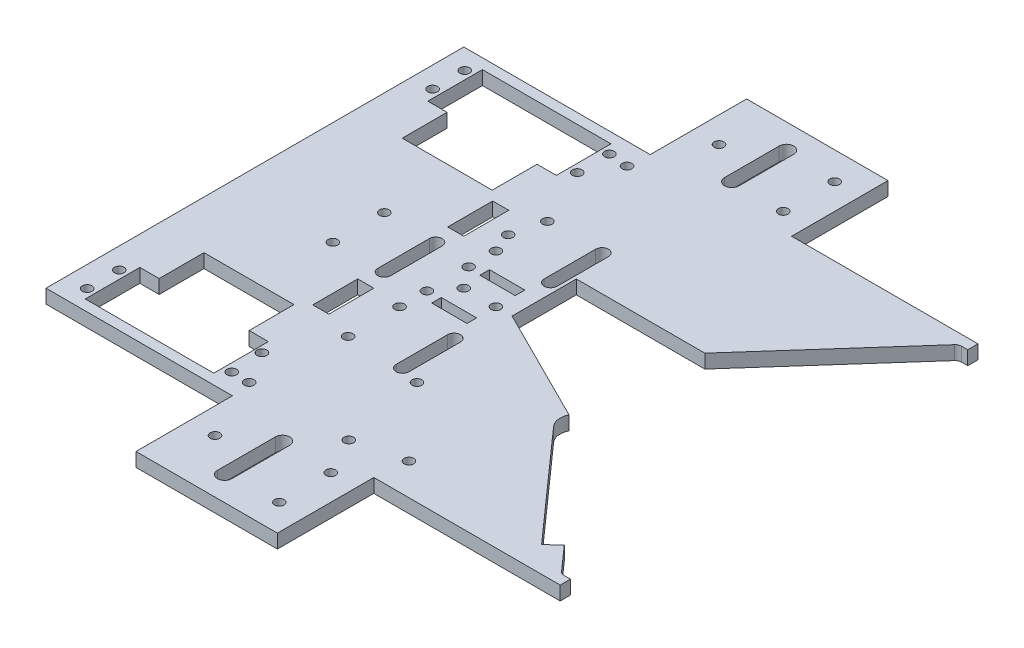
SolidWorks part; units mm, degrees
material "Acrylic (Medium-high impact)"
ref_plane "Front Plane" through (0, 0, 0) normal (0, 0, 1) x (1, 0, 0)
ref_plane "Top Plane" through (0, 0, 0) normal (0, 1, 0) x (1, 0, 0)
ref_plane "Right Plane" through (0, 0, 0) normal (1, 0, 0) x (0, 0, -1)
sketch "Sketch2" plane through (0, 0, 0) normal (0, 1, 0) x (1, 0, 0)
  line L2 (0, 0) -> (0, 65)
  line L3 (0, 65) -> (58, 65)
  line L4 (160, 0) -> (160, 65)
  line L8 (0, 0) -> (160, 0)
  line L9 (102, 65) -> (160, 65)
  line L11 (102, 65) -> (102, 95)
  line L12 (58, 65) -> (58, 95)
  line L13 (58, 95) -> (102, 95)
  dimension "D1" = 65
  dimension "D2" = 160
  dimension "D3" = 44
  dimension "D4" = 30
extrude "Boss-Extrude1" add sketch "Sketch2" along normal blind 4.3
mirror "Mirror1" about plane through (0, 4.3, 0) normal (0, 0, -1) of bodies 101
sketch "Sketch3" plane through (0, 4.3, 0) normal (0, 1, 0) x (1, 0, 0)
  line L0 (160, 61.8) -> (160, -61.8)
  line L1 (120.0126, 20) -> (157.1565, 61.8)
  line L3 (80.0126, 0) -> (80.0126, 20)
  line L4 (80.0126, 20) -> (120.0126, 20)
  line L12 (160, 65) -> (102, 65)
  line L13 (102, 65) -> (102, 95)
  line L15 (102, 95) -> (58, 95)
  line L16 (58, 65) -> (0, 65)
  line L17 (0, 65) -> (0, -65)
  line L18 (0, -65) -> (58, -65)
  line L20 (58, 95) -> (58, 65)
  line L22 (102, -65) -> (160, -65)
  line L23 (160, -65) -> (160, 65)
  line L36 (58, -65) -> (58, -95)
  line L38 (58, -95) -> (102, -95)
  line L39 (58, -95) -> (102, -95)
  line L40 (102, -95) -> (102, -65)
  line L42 (160, -61.8) -> (157.1556, -61.8)
  line L45 (160, 61.8) -> (157.1565, 61.8)
  line L48 (80.0126, 0) -> (120, -20)
  line L49 (120, -20) -> (157.1556, -61.8)
  line M24 (160, -65) -> (160, 65)
  dimension "D2" = 130
  dimension "D3" = 20
  dimension "D4" = 40
  dimension "D1" = 0
extrude "Cut-Extrude1" cut sketch "Sketch3" against normal blind 4.5 contours L48 L49 L1 L4 L3 M24 region at (132.7054, 4.3, -1.1594)
fillet "Fillet1" radius 2 2 edges at (157.1565, 2.15, -61.8) (157.1556, 2.15, 61.8)
ref_axis "Axis1" through (80, 4.3, 95) along (0, 0, -1)
sketch "Sketch4" plane through (0, 4.3, 0) normal (0, 1, 0) x (1, 0, 0)
  line L0 (80, -95) -> (80, 95)
  line L1 (102, -95) -> (58, -95) construction
  line L2 (102, 95) -> (58, 95) construction
ref_plane "Plane2" through (0, 4.3, 0) normal (0, 1, 0) x (1, 0, 0)
sketch "Sketch6" plane through (0, 4.3, 0) normal (0, 1, 0) x (1, 0, 0)
  line L3 (9, -61.8) -> (49, -61.8)
  line L6 (29, -45.8) -> (29, -44.8)
  line L7 (9, -44.8) -> (15, -44.8)
  line L11 (43, -44.8) -> (43, -30.8418)
  line L12 (15, -44.8) -> (15, -30.8418)
  line L13 (15, -30.8418) -> (43, -30.8418)
  line L15 (0, 0) -> (80.0126, 0)
  line L16 (80.0126, 0) -> (120, -20) construction
  line L18 (9, 44.8) -> (15, 44.8)
  line L20 (15, 30.8418) -> (43, 30.8418)
  line L21 (15, 44.8) -> (15, 30.8418)
  line L22 (43, 44.8) -> (43, 30.8418)
  line L25 (15, -45.8) -> (15, -30.8418) construction
  line L27 (9, 61.8) -> (49, 61.8)
  line L30 (4, -61.8) -> (3, -61.8)
  line L31 (0, -61.8) -> (160, -61.8) construction
  line L32 (3, -61.8) -> (4, -61.8)
  line L33 (3, -44.8) -> (3, -62.8) construction
  line L34 (3, -62.8) -> (55, -62.8) construction
  line L35 (55, -44.8) -> (55, -62.8) construction
  line L36 (4, -61.8) -> (54, -61.8) construction
  line L37 (0, 61.8) -> (160, 61.8) construction
  line L38 (54, 61.8) -> (55, 61.8)
  line L39 (54, 61.8) -> (55, 61.8)
  line L40 (43, 44.8) -> (49, 44.8)
  line L41 (4, -45.8) -> (4, -61.8) construction
  line L42 (4, -45.8) -> (54, -45.8) construction
  line L43 (43, -44.8) -> (49, -44.8)
  line L44 (3, -44.8) -> (55, -44.8) construction
  line L45 (29, -45.8) -> (29, -30.8418) construction
  line L46 (43, -45.8) -> (43, -30.8418) construction
  line L47 (54, -45.8) -> (54, -61.8) construction
  line L48 (9, -61.8) -> (49, -61.8)
  line L52 (9, 61.8) -> (9, 44.8)
  line L53 (55, 61.8) -> (54, 61.8)
  line L56 (49, 61.8) -> (49, 44.8)
  line L59 (3, -61.8) -> (4, -61.8)
  line L60 (9, -44.8) -> (9, -61.8)
  line L64 (49, -44.8) -> (49, -61.8)
  dimension "D4" = 1
  dimension "D5" = 14
  dimension "D6" = 14
extrude "Cut-Extrude2" cut sketch "Sketch6" against normal blind 10
sketch "Sketch8" plane through (0, 4.3, 0) normal (0, 1, 0) x (1, 0, 0)
  circle A0 centre (6.5, 58.8) radius 1.5
  circle A1 centre (6.5, 48.8) radius 1.5
  circle A2 centre (51.5, 48.8) radius 1.5
  circle A3 centre (51.5, 58.8) radius 1.5
  circle A4 centre (6.5, -48.7) radius 1.5
  circle A5 centre (6.5, -58.7) radius 1.5
  circle A6 centre (51.5, -58.7) radius 1.5
  circle A7 centre (51, -48.8) radius 1.5
  dimension "D7" = 3
extrude "Cut-Extrude3" cut sketch "Sketch8" against normal blind 10
sketch "Sketch9" plane through (0, 0, 0) normal (0, -1, 0) x (1, 0, 0)
  line L0 (75.75, 69.4) -> (75.75, 87.4)
  line L1 (75.75, -87.4) -> (75.75, -70.4)
  line L2 (80.25, -87.4) -> (80.25, -70.4)
  line L4 (80.25, 69.4) -> (80.25, 87.4)
  circle A0 centre (94, 70.4) radius 1.5
  circle A1 centre (66, 78.4) radius 1.5
  circle A2 centre (66, -78.4) radius 1.5
  circle A3 centre (94, -86.4) radius 1.5
  circle A4 centre (94, 86.4) radius 1.5
  circle A5 centre (94, -70.4) radius 1.5
  arc A6 (75.75, -87.4) -> (80.25, -87.4) centre (78, -87.4) ccw
  arc A7 (80.25, -70.4) -> (75.75, -70.4) centre (78, -70.4) ccw
  arc A10 (75.75, 69.4) -> (80.25, 69.4) centre (78, 69.4) ccw
  arc A12 (80.25, 87.4) -> (75.75, 87.4) centre (78, 87.4) ccw
  dimension "D1" = 3
extrude "Cut-Extrude4" cut sketch "Sketch9" against normal blind 10
sketch "Sketch7" plane through (0, 4.3, 0) normal (0, 1, 0) x (1, 0, 0)
  line L0 (0, 0) -> (80.0126, 0)
  line L1 (0, 65) -> (0, -65) construction
  line L2 (80.0126, 0) -> (80.0126, 20) construction
  line L3 (80, -95) -> (80, 95) construction
  line L4 (64, -9) -> (75, -9)
  line L5 (64, -6) -> (75, -6)
  line L6 (64, -9) -> (64, -6)
  line L7 (75, -9) -> (75, -6)
  line L8 (64, -7.5) -> (75, -7.5)
  line L9 (64, 7.5) -> (75, 7.5)
  line L10 (75, 9) -> (75, 6)
  line L11 (64, 9) -> (64, 6)
  line L12 (64, 6) -> (75, 6)
  line L13 (64, 9) -> (75, 9)
  circle A0 centre (60.0126, -6.5) radius 1.5
  circle A1 centre (60.0126, 6.5) radius 1.5
  dimension "D1" = 3
  dimension "D2" = 6.5
  dimension "D3" = 20
  dimension "D6" = 11
  dimension "D4" = 5
  dimension "D5" = 3
  dimension "D7" = 7.5
sketch "Sketch10" plane through (0, 4.3, 0) normal (0, 1, 0) x (1, 0, 0)
  line L0 (120, -20) -> (156.5589, -61.1287) construction
  line L1 (123.3218, -23.737) -> (149.8964, -53.6334)
  line L2 (116.263, -23.3218) -> (146.1593, -56.9552)
  line L3 (149.8964, -53.6334) -> (146.1593, -56.9552)
  line L4 (120, -20) -> (156.5589, -61.1287) construction
  line L5 (116.263, -23.3218) -> (152.8218, -64.4505) construction
  arc A0 (123.3218, -23.737) -> (116.263, -23.3218) centre (120, -20) ccw
  dimension "D1" = 5
  dimension "D2" = 45
extrude "Cut-Extrude5" cut sketch "Sketch10" against normal blind 10
sketch "Sketch11" plane through (0, 0, 0) normal (0, -1, 0) x (1, 0, 0)
  line L0 (0, 0) -> (80.0126, 0) construction
  line L1 (80, 95) -> (80, -95) construction
  line L2 (80.0126, 0) -> (0, 0)
  line L4 (75, 31.0313) -> (75, 15.0313)
  line L6 (79, 31.0313) -> (79, 15.0313)
  line L7 (79, -31.0313) -> (79, -15.0313)
  line L8 (75, -31.0313) -> (75, -15.0313)
  circle A0 centre (60, 31) radius 1.5
  circle A1 centre (60, 15) radius 1.5
  arc A2 (75, 31.0313) -> (79, 31.0313) centre (77, 31.0313) cw
  arc A3 (75, 15.0313) -> (79, 15.0313) centre (77, 15.0313) ccw
  arc A4 (75, -15.0313) -> (79, -15.0313) centre (77, -15.0313) cw
  arc A5 (75, -31.0313) -> (79, -31.0313) centre (77, -31.0313) ccw
  circle A6 centre (60, -15) radius 1.5
  circle A7 centre (60, -31) radius 1.5
  dimension "D1" = 3
  dimension "D2" = 16
  dimension "D3" = 15
  dimension "D4" = 20
  dimension "D5" = 15
  dimension "D6" = 4
extrude "Cut-Extrude6" cut sketch "Sketch11" against normal blind 10 contours L4 A3 L6 A2 | L8 A5 L7 A4 | A7 | A0 | A1 | A6 region at (77, 0, 23.0313) region at (77, 0, -23.0313) region at (60, 0, -31)
sketch "Sketch12" plane through (0, 0, 0) normal (0, -1, 0) x (-1, 0, 0)
  line L0 (0, 0) -> (-80.0126, 0) construction
  line L3 (-50.2627, -8) -> (-50.2627, 8)
  line L4 (-50.2627, 0) -> (-46.2627, 0)
  line L5 (-46.2627, -8) -> (-46.2627, 8)
  line L6 (0, 0) -> (-46.2627, 0)
  line L7 (0, 65) -> (0, -65) construction
  line L8 (-160, -61.8) -> (0, -61.8) construction
  line L9 (-80.0126, 0) -> (-50.2627, 0)
  line L10 (-80.0126, 0) -> (-115.5281, -17.7634) construction
  line L11 (-80.0126, 0) -> (-80.0126, 20) construction
  line L12 (-58, -65) -> (0, -65) construction
  line L13 (-58, 65) -> (0, 65) construction
  circle A0 centre (-32.2627, -8) radius 1.5
  circle A1 centre (-32.2627, 8) radius 1.5
  arc A2 (-46.2627, 8) -> (-50.2627, 8) centre (-48.2627, 8) ccw
  arc A3 (-50.2627, -8) -> (-46.2627, -8) centre (-48.2627, -8) ccw
  circle A5 centre (-32.2627, -8) radius 1.5 construction
  circle A6 centre (-32.2627, 8) radius 1.5 construction
  dimension "D1" = 3
  dimension "D8" = 8
  dimension "D9" = 8
  dimension "D2" = 8
  dimension "D3" = 14
  dimension "D4" = 4
  dimension "D5" = 61.8
  dimension "D6" = 65
  dimension "D7" = 65
extrude "Cut-Extrude7" cut sketch "Sketch12" against normal blind 10 contours A3 L5 L4 L3 | L4 L5 A2 L3 | A0 | A1 region at (48.2627, 0, 4.7958) region at (48.2627, 0, -4.7958) region at (32.2627, 0, 8) region at (32.2627, 0, -8)
extrude "Cut-Extrude8" cut sketch "Sketch7" against normal blind 9 contours A0 | L4 L7 L5 L6 | L12 L10 L13 L11 | A1
sketch "Sketch13" plane through (0, 4.3, 0) normal (0, 1, 0) x (1, 0, 0)
  line L0 (80.0126, 0) -> (59.0194, 0)
  line L1 (80, -95) -> (80, 95) construction
  circle A0 centre (65, 0) radius 1.5
  circle A1 centre (75, 0) radius 1.5
  dimension "D2" = 3
  dimension "D3" = 5
  dimension "D1" = 10
extrude "Cut-Extrude9" cut sketch "Sketch13" against normal blind 10 contours L0 A0 | L0 A0 | L0 A1 | L0 A1 region at (75, 4.3, 0.6366) region at (75, 4.3, -0.6366) region at (65, 4.3, 0.6366) region at (65, 4.3, -0.6366)
sketch "Sketch14" plane through (0, 4.3, 0) normal (0, 1, 0) x (1, 0, 0)
  circle A0 centre (57.5, 58.3) radius 1.5
  circle A2 centre (57.5, 21.3) radius 1.5
  circle A3 centre (83.1278, -32.706) radius 1.5
  circle A4 centre (103.0587, -55.1282) radius 1.5
  dimension "D1" = 3
  dimension "D2" = 3
extrude "Cut-Extrude10" cut sketch "Sketch14" against normal blind 10
sketch "Sketch15" plane through (0, 4.3, 0) normal (0, 1, 0) x (1, 0, 0)
  line L1 (46, 28) -> (51, 28)
  line L2 (46, 28) -> (46, 14)
  line L3 (46, 14) -> (51, 14)
  line L4 (51, 28) -> (51, 14)
  line L6 (0, 65) -> (0, -65) construction
  line L7 (80.0126, 0) -> (53.7017, 0)
  line L8 (46, -14) -> (51, -14)
  line L9 (51, -28) -> (51, -14)
  line L10 (46, -28) -> (51, -28)
  line L11 (46, -28) -> (46, -14)
  arc A0 (50.2627, 8) -> (46.2627, 8) centre (48.2627, 8) ccw construction
  arc A1 (46.2627, -8) -> (50.2627, -8) centre (48.2627, -8) ccw construction
  dimension "D1" = 46
  dimension "D2" = 5
  dimension "D3" = 14
  dimension "D4" = 14
  dimension "D5" = 14
  dimension "D6" = 6
  dimension "D7" = 6
extrude "Cut-Extrude11" cut sketch "Sketch15" against normal blind 10 contours L4 L1 L2 L3 | L11 L10 L9 L8 region at (48.5, 4.3, -21) region at (48.5, 4.3, 21)
sketch "Sketch16" plane through (0, 4.3, 0) normal (0, 1, 0) x (1, 0, 0)
  circle A0 centre (88, -58.8) radius 1.5
  circle A1 centre (57, -58.8) radius 1.5
  dimension "D1" = 3
extrude "Cut-Extrude12" cut sketch "Sketch16" against normal blind 10
